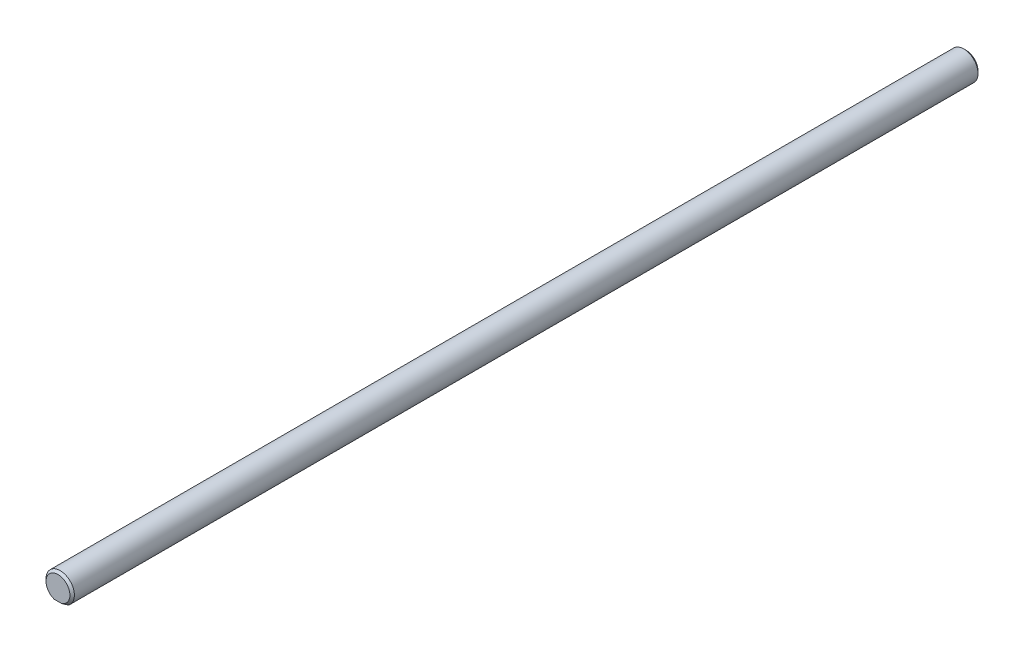
SolidWorks part; units mm, degrees
ref_plane "Front" through (0, 0, 0) normal (0, 0, 1) x (1, 0, 0)
ref_plane "Top" through (0, 0, 0) normal (0, 1, 0) x (1, 0, 0)
ref_plane "Right" through (0, 0, 0) normal (1, 0, 0) x (0, 0, -1)
sketch "Sketch1" plane through (0, 0, 0) normal (0, 0, 1) x (1, 0, 0)
  line L0 (-1.905, -2.54) -> (1.905, -2.54)
  circle A0 centre (0, 0) radius 3.175 construction
  arc A1 (-1.905, -2.54) -> (1.905, -2.54) centre (0, 0) cw
  dimension "D1" = 6.35
  dimension "D2" = 5.715
sketch "Sketch2" plane through (0, 0, 0) normal (0, 1, 0) x (1, 0, 0)
  line L0 (0, -101.6) -> (0, 101.6)
  point P3 (0, 0)
  dimension "D1" = 203.2
sweep "Sweep1" add profiles "Sketch1" path "Sketch2"
chamfer "Chamfer1" distance 0.5 angle 45 2 edges at (0, 3.175, -101.6) (0, 3.175, 101.6)
ref_axis "Axis1" through (0, 0, -101.1) along (0, 0, 1)
